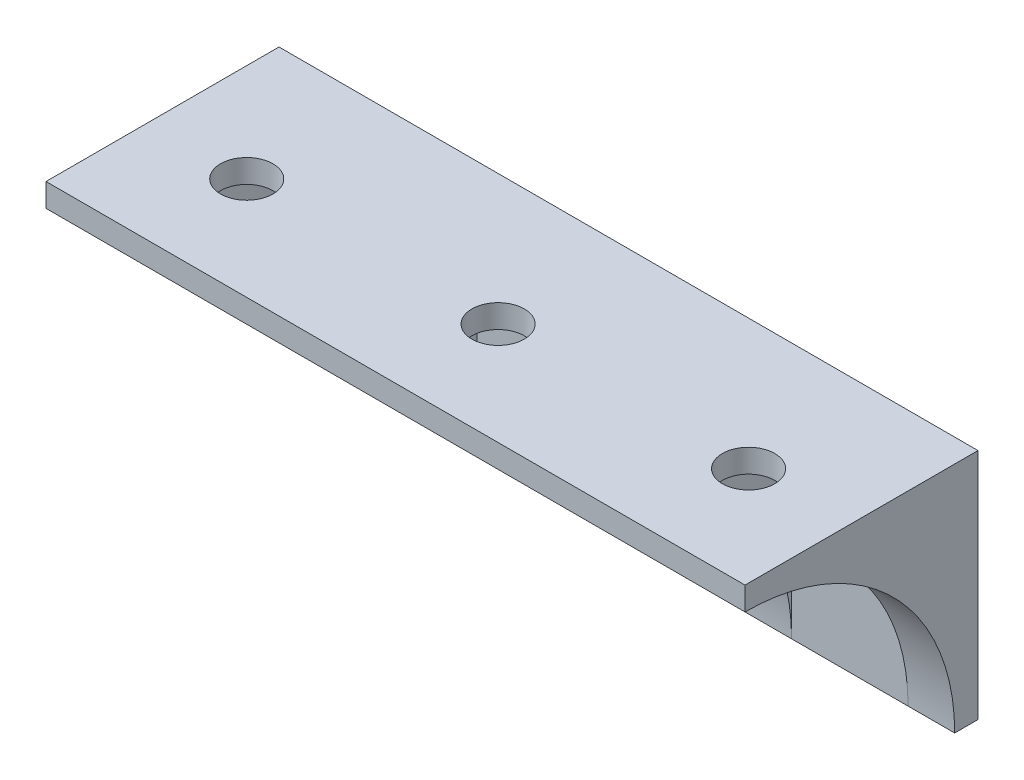
SolidWorks part; units mm, degrees
ref_plane "정면" through (0, 0, 0) normal (0, 0, 1) x (1, 0, 0)
ref_plane "윗면" through (0, 0, 0) normal (0, 1, 0) x (1, 0, 0)
ref_plane "우측면" through (0, 0, 0) normal (1, 0, 0) x (0, 0, -1)
sketch "스케치1" plane through (0, 0, 0) normal (0, 0, 1) x (1, 0, 0)
  line L1 (-30, 10) -> (30, 10)
  line L2 (-30, 10) -> (-30, -10)
  line L3 (-30, -10) -> (30, -10)
  line L4 (30, 10) -> (30, -10)
  line L5 (-30, 10) -> (30, -10) construction
  line L6 (-30, -10) -> (30, 10) construction
  point P0 (0, 0)
  dimension "D1" = 20
  dimension "D2" = 60
extrude "보스-돌출1" add sketch "스케치1" along normal blind 2
sketch "스케치2" plane through (0, 0, 2) normal (0, 0, 1) x (1, 0, 0)
  line L0 (30, -10) -> (30, 10) construction
  line L1 (-30, 10) -> (30, 10)
  line L2 (-30, 10) -> (-30, 8)
  line L3 (-30, 8) -> (30, 8)
  line L4 (30, 10) -> (30, 8)
  dimension "D1" = 2
extrude "보스-돌출2" add sketch "스케치2" along normal blind 18
fillet "필렛1" radius 18 1 edges at (0, 8, 2)
sketch "스케치4" plane through (0, 0, 20) normal (0, 0, 1) x (1, 0, 0)
  line L0 (-30, 8) -> (30, 8) construction
  line L1 (-26, 8) -> (-16, 8)
  line L2 (-26, 8) -> (-26, -10)
  line L3 (-26, -10) -> (-16, -10)
  line L4 (-16, 8) -> (-16, -10)
  line L5 (-30, -10) -> (30, -10) construction
  line L6 (-30, 8) -> (-30, -10) construction
  line L7 (-11, 8) -> (11, 8)
  line L8 (-11, 8) -> (-11, -10)
  line L9 (-11, -10) -> (11, -10)
  line L10 (11, 8) -> (11, -10)
  line L11 (16, 8) -> (26, 8)
  line L12 (16, 8) -> (16, -10)
  line L13 (16, -10) -> (26, -10)
  line L14 (26, 8) -> (26, -10)
  line L15 (30, -10) -> (30, 8) construction
  dimension "D1" = 4
  dimension "D2" = 5
  dimension "D3" = 4
  dimension "D4" = 5
  dimension "D5" = 10
  dimension "D6" = 10
extrude "컷-돌출1" cut sketch "스케치4" against normal blind 18
hole_wizard "M4 여유 구멍1" positions "스케치5" profile "스케치6" hole size "M4" standard "KS" end condition through all
sketch "스케치5" plane through (0, 8, 0) normal (0, -1, 0) x (-1, 0, 0)
  point P0 (-21.4987, -11.1913)
  point P2 (21.5793, -11.1913)
  point P7 (0, -11.1913)
sketch "스케치6" plane through (21.4987, 8, 11.1913) normal (1, 0, 0) x (0, 0, -1)
  line L0 (0, 0) -> (0, 2)
  line L1 (0, 2) -> (2.25, 2)
  line L2 (2.25, 2) -> (2.25, 0)
  line L5 (2.25, 0) -> (0, 0)
  line L11 (0, -6.35) -> (0, 107.95) construction
  dimension "관통 구멍 지름" = 4.5
  dimension "관통 구멍 깊이" = 2
